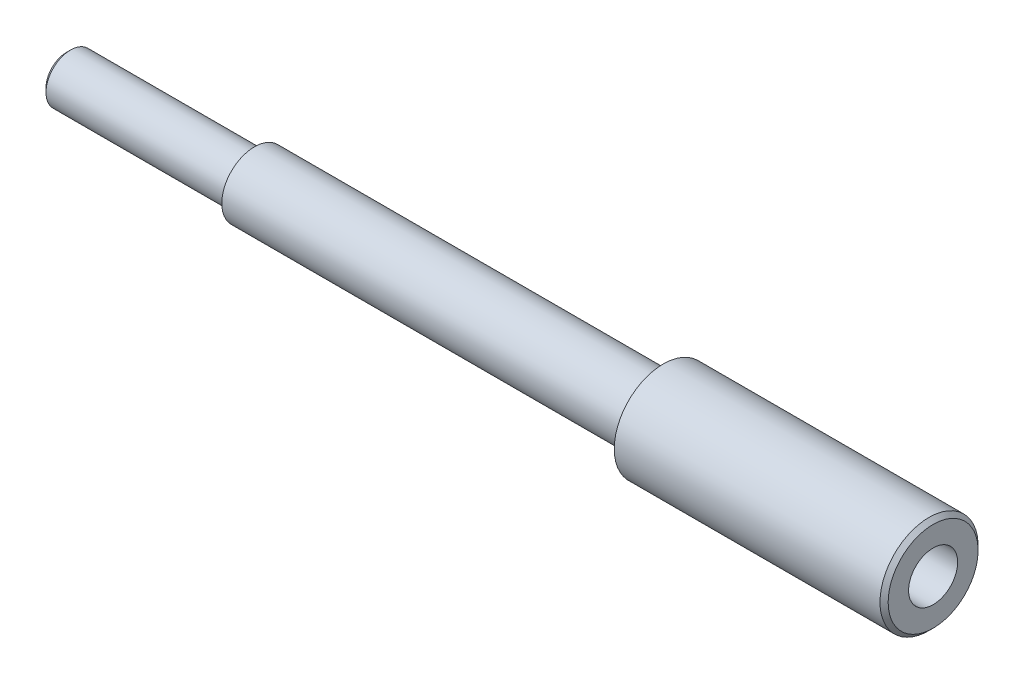
SolidWorks part; units mm, degrees
material "AISI 1045 Steel, cold drawn"
ref_plane "Front Plane" through (0, 0, 0) normal (0, 0, 1) x (1, 0, 0)
ref_plane "Top Plane" through (0, 0, 0) normal (0, 1, 0) x (1, 0, 0)
ref_plane "Right Plane" through (0, 0, 0) normal (1, 0, 0) x (0, 0, -1)
other "Configuration Table"
sketch "Sketch_Shaft_Profile" plane through (0, 0, 0) normal (0, 0, 1) x (1, 0, 0)
  line L0 (-5, 0) -> (110, 0) construction
  line L1 (0, 0) -> (0, 2.5)
  line L2 (0, 2.5) -> (0.5, 3)
  line L3 (0.5, 3) -> (23, 3)
  line L4 (23, 3) -> (23, 4)
  line L5 (23, 4) -> (73, 4)
  line L6 (73, 4) -> (73, 6)
  line L7 (73, 6) -> (105.5, 6)
  line L8 (105.5, 6) -> (106, 5.5)
  line L9 (106, 5.5) -> (106, 3)
  line L10 (106, 3) -> (92, 3)
  line L11 (92, 3) -> (92, 0)
  line L12 (92, 0) -> (0, 0)
revolve "Shaft_Revolve_12x33_8x50_M6x23_TappedM6x14" add sketch "Sketch_Shaft_Profile" angle 360 about L0
ref_axis "Shaft_Axis_X" through (106.7263, 0, 0) along (-1, 0, 0)
